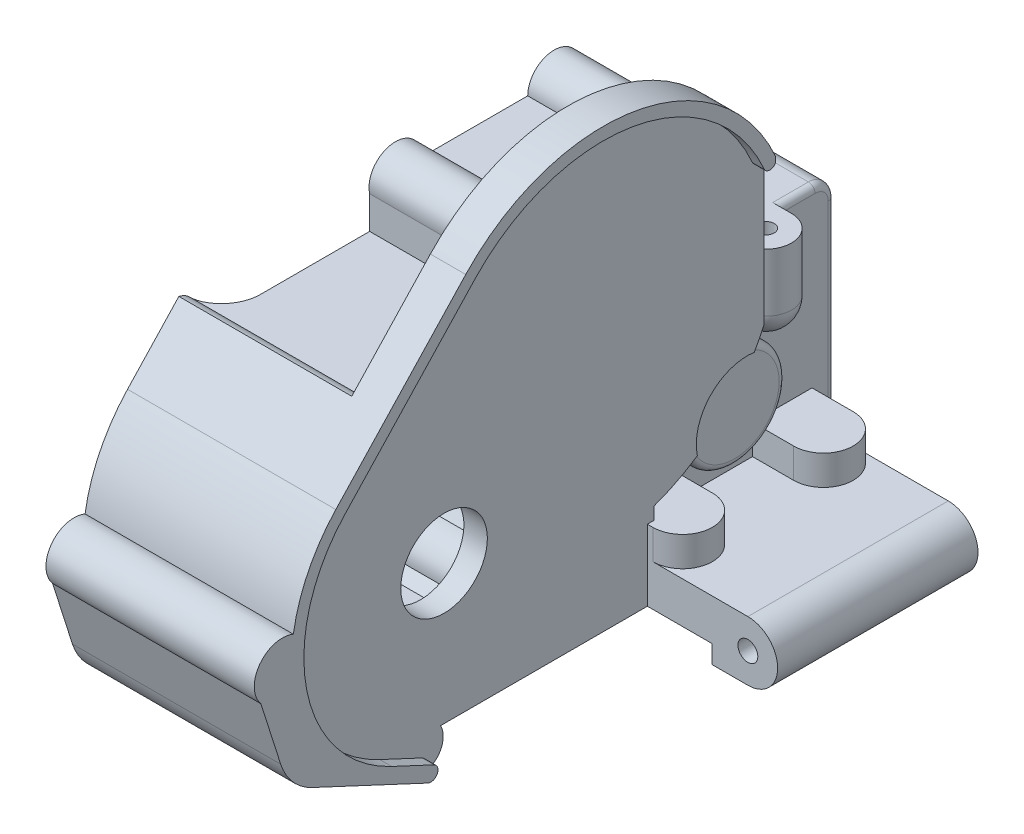
SolidWorks part; units mm, degrees
ref_plane "Front Plane" through (0, 0, 0) normal (0, 0, 1) x (1, 0, 0)
ref_plane "Top Plane" through (0, 0, 0) normal (0, 1, 0) x (1, 0, 0)
ref_plane "Right Plane" through (0, 0, 0) normal (1, 0, 0) x (0, 0, -1)
sketch "Sketch1" plane through (0, 0, 0) normal (0, 0, 1) x (1, 0, 0)
  line L0 (32.75, 0) -> (-32.75, 0) construction
  line L1 (32.75, -4.5) -> (-32.75, -4.5)
  line L2 (32.75, 4.5) -> (-32.75, 4.5)
  line L4 (-27.3, -4.5) -> (27.3, -4.5)
  line L5 (-27.3, -4.5) -> (-27.3, -1.75)
  line L6 (-27.3, -1.75) -> (27.3, -1.75)
  line L7 (27.3, -4.5) -> (27.3, -1.75)
  arc A0 (32.75, -4.5) -> (32.75, 4.5) centre (32.75, 0) ccw
  arc A1 (-32.75, 4.5) -> (-32.75, -4.5) centre (-32.75, 0) ccw
  circle A2 centre (32.75, 0) radius 1.5
  circle A3 centre (-32.75, 0) radius 1.5
  point P2 (0, 0)
  point P12 (0, -1.75)
  dimension "D5" = 3
  dimension "D1" = 65.5
  dimension "D2" = 9
  dimension "D3" = 54.6
  dimension "D4" = 2.75
extrude "Boss-Extrude1" add sketch "Sketch1" along normal blind 30.3 contours L2 A1 L1 L5 L6 L7 A0 region at (0, 0.9599, 0)
sketch "Sketch2" plane through (0, 0, 0) normal (1, 0, 0) x (0, 0, -1)
  line L0 (-35.05, -1.75) -> (3.45, -1.75)
  line L1 (3.45, -1.75) -> (3.45, 32.25)
  line L2 (0.45, 35.25) -> (-15.05, 35.25)
  line L3 (-35.05, 15.25) -> (-35.05, -1.75)
  line L4 (-35.05, -1.75) -> (-70.7928, -1.75)
  line L5 (-30.3, -1.75) -> (0, -1.75) construction
  line L6 (0, -4.5) -> (0, 4.5) construction
  line L7 (-47.969, 0.15) -> (-74.131, 0.15)
  line L8 (-66.9229, -5.75) -> (-82.7794, 1.65)
  line L9 (-87.55, 7.078) -> (-90.55, 16.5114)
  line L11 (-59.5712, 57.2396) -> (-79.2177, 36.2777)
  line L12 (-12.7, 49.25) -> (-12.7, 35.25)
  line L13 (-61.175, -3.35) -> (-61.175, -1.75)
  arc A0 (-15.05, 35.25) -> (-35.05, 15.25) centre (-15.05, 15.25) ccw
  arc A1 (3.45, 32.25) -> (0.45, 35.25) centre (0.45, 32.25) ccw
  circle A2 centre (-61.05, 19.25) radius 23.15
  circle A3 centre (-64.55, -3.35) radius 3.375
  arc A4 (-87.55, 7.078) -> (-82.7794, 1.65) centre (-78.9733, 9.8056) ccw
  circle A5 centre (-87.3, 19.25) radius 4.25
  arc A6 (-85.6407, 23.1627) -> (-79.2177, 36.2777) centre (-61.05, 19.25) cw
  arc A7 (-12.7, 49.25) -> (-59.5712, 57.2396) centre (-38.7768, 37.75) ccw
  point P13 (3.45, 35.25)
  point P30 (-91.55, 19.25)
  point P35 (-38.7768, 66.25)
  dimension "D2" = 20
  dimension "D5" = 3
  dimension "D7" = 46.3
  dimension "D12" = 6.75
  dimension "D13" = 8.5
  dimension "D16" = 9
  dimension "D20" = 1.75
  dimension "D21" = 28.5
  dimension "D1" = 3.45
  dimension "D3" = 37
  dimension "D4" = 18.5
  dimension "D6" = 46
  dimension "D8" = 21
  dimension "D9" = 1.9
  dimension "D10" = 68
  dimension "D11" = 1.6
  dimension "D14" = 95
  dimension "D15" = 1.5
  dimension "D17" = 4
  dimension "D18" = 1
  dimension "D19" = 91
  dimension "D22" = 16.15
  dimension "D23" = 68
  dimension "D24" = 14
extrude "Boss-Extrude2" add sketch "Sketch2" along normal mid plane 24.3 contours L1 A1 L2 A0 L3 L0 | A7 L11 A6 A5 A2 L4 L3 A0 | A5 A2 L7 | A3 L4 A2 L7 | L4 A3 A2 | L4 A3 | A5 L9 A4 L8 A3 A2 | A2 A5 | A3 L4 A2 | A2 A3 | A2 A5 region at (0, 15.8231, 14.8775) region at (0, 43.4679, 39.2022) region at (0, -0.6991, 60.325) region at (0, -4.871, 64.7855) region at (0, -2.6944, 64.2173) region at (0, 20.1783, 60.9898) region at (0, -1.0211, 64.55) region at (0, 5.9046, 81.7148) region at (0, -2.1301, 68.7916) region at (0, 19.25, 87.5929) region at (0, 19.25, 83.7028)
sketch "Sketch3" plane through (0, 35.25, 0) normal (0, 1, 0) x (1, 0, 0)
  line L0 (14, -8.825) -> (-14, -8.825) construction
  line L1 (14, -12.7) -> (-14, -12.7)
  line L2 (14, -4.95) -> (-14, -4.95)
  line L3 (12.15, 3.45) -> (-12.15, 3.45) construction
  arc A0 (14, -12.7) -> (14, -4.95) centre (14, -8.825) ccw
  arc A1 (-14, -4.95) -> (-14, -12.7) centre (-14, -8.825) ccw
  point P2 (0, -8.825)
  point P7 (-17.875, -8.825)
  point P8 (17.875, -8.825)
  dimension "D1" = 28
  dimension "D2" = 7.75
  dimension "D3" = 8.4
extrude "Boss-Extrude3" add sketch "Sketch3" against normal blind 12.66
fillet "Fillet1" radius 3.875 6 edges at (-13.075, 22.59, 4.95) (-13.075, 22.59, 12.7) (13.075, 22.59, 12.7) (13.075, 22.59, 4.95) (-17.875, 22.59, 8.825) (17.875, 22.59, 8.825)
sketch "Sketch4" plane through (0, 4.5, 0) normal (0, 1, 0) x (1, 0, 0)
  line L0 (-18.375, -4.5) -> (18.375, -4.5) construction
  line L1 (-18.375, 0) -> (18.375, 0)
  line L2 (-18.375, -9) -> (18.375, -9)
  line L3 (32.75, 0) -> (12.15, 0) construction
  line L4 (22.875, -4.5) -> (-22.875, -4.5) construction
  line L5 (18.375, -25.8) -> (-18.375, -25.8) construction
  line L6 (18.375, -30.3) -> (-18.375, -30.3)
  line L7 (18.375, -21.3) -> (-18.375, -21.3)
  line L8 (-12.15, -30.3) -> (-32.75, -30.3) construction
  arc A0 (-18.375, 0) -> (-18.375, -9) centre (-18.375, -4.5) ccw
  arc A1 (18.375, -9) -> (18.375, 0) centre (18.375, -4.5) ccw
  arc A2 (18.375, -30.3) -> (18.375, -21.3) centre (18.375, -25.8) ccw
  arc A3 (-18.375, -21.3) -> (-18.375, -30.3) centre (-18.375, -25.8) ccw
  point P2 (0, -4.5)
  point P10 (-22.875, -4.5)
  point P11 (0, -25.8)
  point P13 (22.875, -4.5)
  point P24 (0, 0)
  dimension "D2" = 4.5
  dimension "D1" = 45.75
extrude "Boss-Extrude4" add sketch "Sketch4" along normal blind 4.5
sketch "Sketch5" plane through (0, 35.25, 0) normal (0, 1, 0) x (1, 0, 0)
  circle A0 centre (14, -8.825) radius 1.25
  circle A1 centre (-14, -8.825) radius 1.25
  dimension "D1" = 2.5
extrude "Cut-Extrude1" cut sketch "Sketch5" against normal blind 10
sketch "Sketch6" plane through (0, 0, 0) normal (1, 0, 0) x (0, 0, -1)
  line L0 (-61.5784, -1.75) -> (-30.3, -1.75) construction
  line L3 (-9, 4.5) -> (-21.3, 4.5) construction
  circle A0 centre (-15.15, 15.75) radius 7.75
  point P2 (-7.4, 15.75)
  point P4 (-15.15, 4.5)
  point P5 (0, 0)
  point P8 (0, 0)
  dimension "D1" = 15.5
  dimension "D2" = 17.5
extrude "Boss-Extrude5" add sketch "Sketch6" along normal mid plane 31.16
fillet "Fillet2" radius 1 2 edges at (-15.58, 15.75, 7.4) (15.58, 15.75, 7.4)
fillet "Fillet3" radius 1 6 edges at (12.15, 35.25, 2.25) (12.15, 34.3713, -2.5713) (-12.15, 35.25, 2.25) (-12.15, 34.3713, -2.5713) (12.15, 15.25, -3.45) (-12.15, 15.25, -3.45)
sketch "Sketch7" plane through (0, -1.75, 0) normal (0, -1, 0) x (1, 0, 0)
  line L0 (-27.3, 0) -> (-12.15, 0) construction
  line L1 (0, -4.95) -> (0, 4.95) construction
  circle A0 centre (-19, 5.2) radius 2
  circle A1 centre (-19, 25.2) radius 2
  circle A2 centre (19, 5.2) radius 2
  circle A3 centre (19, 25.2) radius 2
  dimension "D4" = 4
  dimension "D1" = 20
  dimension "D2" = 19
  dimension "D3" = 5.2
extrude "Cut-Extrude2" cut sketch "Sketch7" against normal blind 8
sketch "Sketch9" plane through (12.15, 0, 0) normal (1, 0, 0) x (0, 0, -1)
  line L0 (-29.3, 10.8718) -> (-29.3, 9)
  line L1 (-21.3, 9) -> (-30.3, 9) construction
  line L2 (-29.3, 9) -> (-30.3, 9)
  line L3 (-30.3, 9) -> (-30.3, -1.75)
  line L21 (-12.7, 35.25) -> (-12.7, 49.25)
  line L22 (0.45, 34.25) -> (-4.95, 34.25)
  line L23 (-4.95, 34.25) -> (-4.95, 26.465)
  line L24 (-12.7, 26.465) -> (-12.7, 35.25)
  line L25 (-12.7, 35.25) -> (-12.7, 49.25)
  line L27 (-59.5712, 57.2396) -> (-79.2177, 36.2777)
  line L28 (-90.55, 16.5114) -> (-87.55, 7.078)
  line L29 (-82.7794, 1.65) -> (-66.9229, -5.75)
  line L30 (-61.5784, -1.75) -> (-30.3, -1.75)
  line L31 (-30.3, -1.75) -> (-30.3, 9)
  line L32 (-30.3, 9) -> (-21.3, 9)
  line L33 (-21.3, 9) -> (-21.3, 4.5)
  line L34 (-21.3, 4.5) -> (-9, 4.5)
  line L35 (-9, 4.5) -> (-9, 9)
  line L36 (-9, 9) -> (0, 9)
  line L37 (0, 9) -> (0, -1.75)
  line L38 (0, -1.75) -> (2.45, -1.75)
  line L39 (2.45, -1.75) -> (2.45, 32.25)
  line L40 (0.45, 34.25) -> (-4.95, 34.25)
  line L41 (-4.95, 34.25) -> (-4.95, 26.465)
  line L42 (-12.7, 26.465) -> (-12.7, 35.25)
  line L45 (-59.5712, 57.2396) -> (-79.2177, 36.2777)
  line L46 (-90.55, 16.5114) -> (-87.55, 7.078)
  line L47 (-82.7794, 1.65) -> (-66.9229, -5.75)
  line L48 (-61.5784, -1.75) -> (-30.3, -1.75)
  line L49 (-30.3, -1.75) -> (-30.3, 9)
  line L50 (-30.3, 9) -> (-21.3, 9)
  line L51 (-21.3, 9) -> (-21.3, 4.5)
  line L52 (-21.3, 4.5) -> (-9, 4.5)
  line L53 (-9, 4.5) -> (-9, 9)
  line L54 (-9, 9) -> (0, 9)
  line L55 (0, 9) -> (0, -1.75)
  line L56 (0, -1.75) -> (2.45, -1.75)
  line L57 (2.45, -1.75) -> (2.45, 32.25)
  circle A0 centre (-38.7768, 37.75) radius 28.5
  circle A1 centre (-15.15, 15.75) radius 7.75 construction
  circle A2 centre (-15.15, 15.75) radius 7.75
  arc A12 (2.45, 32.25) -> (0.45, 34.25) centre (0.45, 32.25) ccw
  arc A13 (-8.825, 22.59) -> (-4.95, 26.465) centre (-8.825, 26.465) ccw
  arc A14 (-12.7, 26.465) -> (-8.825, 22.59) centre (-8.825, 26.465) ccw
  arc A15 (-12.7, 49.25) -> (-59.5712, 57.2396) centre (-38.7768, 37.75) ccw
  arc A16 (-79.2177, 36.2777) -> (-85.6407, 23.1627) centre (-61.05, 19.25) ccw
  arc A17 (-85.6407, 23.1627) -> (-90.55, 16.5114) centre (-87.3, 19.25) ccw
  arc A18 (-87.55, 7.078) -> (-82.7794, 1.65) centre (-78.9733, 9.8056) ccw
  arc A19 (-66.9229, -5.75) -> (-61.5784, -1.75) centre (-64.55, -3.35) ccw
  arc A21 (2.45, 32.25) -> (0.45, 34.25) centre (0.45, 32.25) ccw
  arc A22 (-8.825, 22.59) -> (-4.95, 26.465) centre (-8.825, 26.465) ccw
  arc A23 (-12.7, 26.465) -> (-8.825, 22.59) centre (-8.825, 26.465) ccw
  arc A24 (-12.7, 49.25) -> (-59.5712, 57.2396) centre (-38.7768, 37.75) ccw
  arc A25 (-79.2177, 36.2777) -> (-85.6407, 23.1627) centre (-61.05, 19.25) ccw
  arc A26 (-85.6407, 23.1627) -> (-90.55, 16.5114) centre (-87.3, 19.25) ccw
  arc A27 (-87.55, 7.078) -> (-82.7794, 1.65) centre (-78.9733, 9.8056) ccw
  arc A28 (-66.9229, -5.75) -> (-61.5784, -1.75) centre (-64.55, -3.35) ccw
  point P11 (-29.3, 9.9359)
  circle M31 centre (-15.15, 15.75) radius 7.75
  arc M36 (-8.825, 22.59) -> (-12.7, 26.465) centre (-8.825, 26.465) cw
  line M37 (-12.7, 26.465) -> (-12.7, 35.25)
  arc M40 (-12.7, 49.25) -> (-59.5712, 57.2396) centre (-38.7768, 37.75) ccw
  line M41 (-59.5712, 57.2396) -> (-79.2177, 36.2777)
  arc M42 (-79.2177, 36.2777) -> (-85.6407, 23.1627) centre (-61.05, 19.25) ccw
  arc M43 (-85.6407, 23.1627) -> (-90.55, 16.5114) centre (-87.3, 19.25) ccw
  line M44 (-90.55, 16.5114) -> (-87.55, 7.078)
  arc M45 (-87.55, 7.078) -> (-82.7794, 1.65) centre (-78.9733, 9.8056) ccw
  line M46 (-82.7794, 1.65) -> (-66.9229, -5.75)
  arc M47 (-66.9229, -5.75) -> (-61.5784, -1.75) centre (-64.55, -3.35) ccw
  line M49 (-61.5784, -1.75) -> (-30.3, -1.75)
  line M50 (-30.3, -1.75) -> (-30.3, 9)
  line M51 (-30.3, 9) -> (-21.3, 9)
  line M91 (-12.7, 35.25) -> (-12.7, 49.25)
  dimension "D2" = 1
  dimension "D1" = 0
extrude "Boss-Extrude6" add sketch "Sketch9" along normal offset from surface (5.4 mm away) 29.7 contours A0 L0 M41 M42 M43 M44 M45 M46 M47 M49 M50 M51 | A0 M40 M31 M36 M37 M91 region at (12.15, 14.0433, 66.1845) region at (12.15, 38.0059, 39.4606) up to face at (-12.15, 15.75, 7.4)
sketch "Sketch10" plane through (17.55, 0, 0) normal (1, 0, 0) x (0, 0, -1)
  line L0 (-58.1849, 55.9403) -> (-77.8314, 34.9784)
  line L2 (-66.9229, -5.75) -> (-65.2918, -6.5112)
  line L3 (-70.7767, -1.5921) -> (-64.3876, -4.5738)
  line L8 (-29.3, 9) -> (-29.3, 10.8718)
  line L9 (-12.7, 26.465) -> (-12.7, 49.25)
  line L10 (-59.5712, 57.2396) -> (-79.2177, 36.2777)
  line L11 (-90.55, 16.5114) -> (-87.55, 7.078)
  line L12 (-82.7794, 1.65) -> (-66.9229, -5.75)
  line L13 (-61.5784, -1.75) -> (-30.3, -1.75)
  line L14 (-30.3, -1.75) -> (-30.3, 9)
  line L15 (-30.3, 9) -> (-29.3, 9)
  line L16 (-29.3, 9) -> (-29.3, 10.8718)
  line L17 (-12.7, 26.465) -> (-12.7, 49.25)
  line L18 (-59.5712, 57.2396) -> (-79.2177, 36.2777)
  line L19 (-90.55, 16.5114) -> (-87.55, 7.078)
  line L20 (-82.7794, 1.65) -> (-66.9229, -5.75)
  line L21 (-61.5784, -1.75) -> (-30.3, -1.75)
  line L22 (-30.3, -1.75) -> (-30.3, 9)
  line L23 (-30.3, 9) -> (-29.3, 9)
  circle A0 centre (-61.05, 19.25) radius 23
  arc A1 (-14.4385, 48.4833) -> (-58.1849, 55.9403) centre (-38.7768, 37.75) ccw
  arc A2 (-12.7, 49.25) -> (-14.4385, 48.4833) centre (-13.5692, 48.8667) cw
  arc A5 (-65.2918, -6.5112) -> (-64.3876, -4.5738) centre (-64.8397, -5.5425) ccw
  arc A10 (-29.3, 10.8718) -> (-22.7412, 14.1892) centre (-38.7768, 37.75) ccw
  arc A11 (-14.1338, 23.4331) -> (-22.7412, 14.1892) centre (-15.15, 15.75) ccw
  arc A12 (-14.1338, 23.4331) -> (-12.6947, 26.2621) centre (-38.7768, 37.75) ccw
  arc A13 (-12.7, 26.465) -> (-12.6947, 26.2621) centre (-8.825, 26.465) ccw
  arc A14 (-12.7, 49.25) -> (-59.5712, 57.2396) centre (-38.7768, 37.75) ccw
  arc A15 (-79.2177, 36.2777) -> (-85.6407, 23.1627) centre (-61.05, 19.25) ccw
  arc A16 (-85.6407, 23.1627) -> (-90.55, 16.5114) centre (-87.3, 19.25) ccw
  arc A17 (-87.55, 7.078) -> (-82.7794, 1.65) centre (-78.9733, 9.8056) ccw
  arc A18 (-66.9229, -5.75) -> (-61.5784, -1.75) centre (-64.55, -3.35) ccw
  arc A20 (-29.3, 10.8718) -> (-22.7412, 14.1892) centre (-38.7768, 37.75) ccw
  arc A21 (-14.1338, 23.4331) -> (-22.7412, 14.1892) centre (-15.15, 15.75) ccw
  arc A22 (-14.1338, 23.4331) -> (-12.6947, 26.2621) centre (-38.7768, 37.75) ccw
  arc A23 (-12.7, 26.465) -> (-12.6947, 26.2621) centre (-8.825, 26.465) ccw
  arc A24 (-12.7, 49.25) -> (-59.5712, 57.2396) centre (-38.7768, 37.75) ccw
  arc A25 (-79.2177, 36.2777) -> (-85.6407, 23.1627) centre (-61.05, 19.25) ccw
  arc A26 (-85.6407, 23.1627) -> (-90.55, 16.5114) centre (-87.3, 19.25) ccw
  arc A27 (-87.55, 7.078) -> (-82.7794, 1.65) centre (-78.9733, 9.8056) ccw
  arc A28 (-66.9229, -5.75) -> (-61.5784, -1.75) centre (-64.55, -3.35) ccw
  point P32 (-64.55, -5.509)
  point P34 (-64.8384, -5.5431)
  arc M31 (-12.7, 49.25) -> (-59.5712, 57.2396) centre (-38.7768, 37.75) ccw
  line M32 (-59.5712, 57.2396) -> (-79.2177, 36.2777)
  arc M33 (-79.2177, 36.2777) -> (-85.6407, 23.1627) centre (-61.05, 19.25) ccw
  arc M34 (-85.6407, 23.1627) -> (-90.55, 16.5114) centre (-87.3, 19.25) ccw
  line M35 (-90.55, 16.5114) -> (-87.55, 7.078)
  arc M36 (-87.55, 7.078) -> (-82.7794, 1.65) centre (-78.9733, 9.8056) ccw
  line M37 (-82.7794, 1.65) -> (-66.9229, -5.75)
  dimension "D2" = 1.9
  dimension "D3" = 1.9
  dimension "D4" = 1.8
  dimension "D1" = 0
extrude "Boss-Extrude7" add sketch "Sketch10" along normal offset from surface (1.8 mm away) 31.5 contours L2 A5 L3 A0 L0 A1 A2 L17 M31 M32 M33 M34 M35 M36 M37 region at (17.55, 46.1935, 68.7915) up to face at (-12.15, 15.75, 7.4)
sketch "Sketch8" plane through (-12.15, 0, 0) normal (-1, 0, 0) x (0, 0, 1)
  line L0 (35.05, -1.75) -> (-3.45, -1.75) construction
  line L1 (-3.45, -1.75) -> (-3.45, 32.25) construction
  line L2 (-0.45, 35.25) -> (15.05, 35.25) construction
  line L4 (59.5712, 57.2396) -> (79.2177, 36.2777) construction
  line L5 (35.05, 15.25) -> (35.05, -1.75) construction
  line L6 (35.05, -1.75) -> (70.7928, -1.75) construction
  line L7 (66.9229, -5.75) -> (82.7794, 1.65) construction
  line L8 (87.55, 7.078) -> (90.55, 16.5114) construction
  line L9 (47.969, 0.15) -> (74.131, 0.15) construction
  line L10 (35.05, -1.75) -> (-3.45, -1.75)
  line L11 (-3.45, -1.75) -> (-3.45, 32.25)
  line L12 (-0.45, 35.25) -> (15.05, 35.25)
  line L14 (59.5712, 57.2396) -> (79.2177, 36.2777)
  line L15 (35.05, 15.25) -> (35.05, -1.75)
  line L16 (35.05, -1.75) -> (70.7928, -1.75)
  line L17 (66.9229, -5.75) -> (82.7794, 1.65)
  line L18 (87.55, 7.078) -> (90.55, 16.5114)
  line L19 (47.969, 0.15) -> (74.131, 0.15)
  line L20 (77.9409, 35.081) -> (72.2527, 41.15)
  line L21 (72.2527, 41.15) -> (50.6527, 41.15)
  line L22 (50.6527, 38.6228) -> (50.6527, 41.15)
  line L23 (42.1867, 29.7028) -> (40.1236, 29.15)
  line L24 (70.0027, 41.15) -> (70.0027, 38.469)
  arc A0 (-0.45, 35.25) -> (-3.45, 32.25) centre (-0.45, 32.25) ccw construction
  circle A1 centre (61.05, 19.25) radius 23.15
  circle A2 centre (61.05, 19.25) radius 23.15
  circle A3 centre (87.3, 19.25) radius 4.25
  circle A4 centre (87.3, 19.25) radius 4.25
  circle A5 centre (64.55, -3.35) radius 3.375
  circle A6 centre (64.55, -3.35) radius 3.375
  arc A7 (59.5712, 57.2396) -> (12.7, 49.25) centre (38.7768, 37.75) ccw construction
  arc A8 (85.6407, 23.1627) -> (79.2177, 36.2777) centre (61.05, 19.25) ccw construction
  arc A9 (35.05, 15.25) -> (15.05, 35.25) centre (15.05, 15.25) ccw construction
  arc A10 (82.7794, 1.65) -> (87.55, 7.078) centre (78.9733, 9.8056) ccw construction
  arc A11 (-0.45, 35.25) -> (-3.45, 32.25) centre (-0.45, 32.25) ccw
  arc A12 (59.5712, 57.2396) -> (12.7, 49.25) centre (38.7768, 37.75) ccw
  arc A13 (85.6407, 23.1627) -> (79.2177, 36.2777) centre (61.05, 19.25) ccw
  arc A14 (35.05, 15.25) -> (15.05, 35.25) centre (15.05, 15.25) ccw
  arc A15 (82.7794, 1.65) -> (87.55, 7.078) centre (78.9733, 9.8056) ccw
  arc A16 (43.3544, 30.5577) -> (49.7307, 36.9382) centre (61.05, 19.25) cw
  arc A17 (43.3544, 30.5577) -> (42.1867, 29.7028) centre (41.6691, 31.6346) cw
  arc A18 (49.7307, 36.9382) -> (50.6527, 38.6228) centre (48.6527, 38.6228) ccw
  circle A19 centre (42.05, 1.8) radius 4.25
  circle A20 centre (72.2527, 41.15) radius 3.5
  point P48 (51.2409, 41.15)
  point P49 (70.049, 38.469)
  dimension "D5" = 2
  dimension "D8" = 8.5
  dimension "D10" = 21
  dimension "D12" = 7
  dimension "D4" = 41
  dimension "D6" = 3.55
  dimension "D7" = 45.5
  dimension "D9" = 12
  dimension "D11" = 105
  dimension "D13" = 19.35
  dimension "D14" = 2.25
  dimension "D1" = 0
  dimension "D2" = 0
  dimension "D3" = 0
extrude "Cut-Extrude3" cut sketch "Sketch8" against normal blind 26.15 and the other way through all contours A20 A2 L21 L22 A18 A16 A17 L23 A19 L19 A4 | A2 A20 L24 | L21 A20 A2 L24 | A20 L21 A2 region at (-12.15, 19.7067, 61.283) region at (-12.15, 41.127, 68.6868) region at (-12.15, 40.9664, 69.5434) region at (-12.15, 39.95, 69.4846)
sketch "Sketch11" plane through (-12.15, 0, 0) normal (-1, 0, 0) x (0, 0, 1)
  line L0 (12.7, 35.25) -> (4.95, 35.25) construction
  line L1 (12.7, 35.0955) -> (12.7, 36.75)
  line L2 (12.7, 49.25) -> (12.7, 35.25) construction
  line L3 (12.7, 35.25) -> (12.7941, 35.25)
  line L4 (70.0027, 41.15) -> (53.5458, 41.15) construction
  line L5 (69.8032, 43.65) -> (47.6032, 43.65)
  line L6 (35.1146, 24.75) -> (38.5628, 24.75)
  line L7 (61.5784, -1.75) -> (30.3, -1.75) construction
  line L8 (47.6032, 43.65) -> (47.6032, 48.5754)
  line L9 (23.7, 49.45) -> (39.7, 49.45)
  line L26 (4.95, 26.465) -> (4.95, 34.25)
  line L27 (4.95, 34.25) -> (-0.45, 34.25)
  line L28 (-2.45, 32.25) -> (-2.45, -1.75)
  line L29 (-2.45, -1.75) -> (0, -1.75)
  line L30 (0, -1.75) -> (0, 9)
  line L31 (0, 9) -> (9, 9)
  line L32 (9, 9) -> (9, 4.5)
  line L33 (9, 4.5) -> (21.3, 4.5)
  line L34 (21.3, 4.5) -> (21.3, 9)
  line L35 (21.3, 9) -> (30.3, 9)
  line L36 (30.3, 9) -> (30.3, -1.75)
  line L37 (30.3, -1.75) -> (61.5784, -1.75)
  line L38 (66.9229, -5.75) -> (82.7794, 1.65)
  line L39 (87.55, 7.078) -> (90.55, 16.5114)
  line L40 (79.2177, 36.2777) -> (59.5712, 57.2396)
  line L41 (12.7, 49.25) -> (12.7, 35.25)
  line L42 (12.7, 35.25) -> (12.7, 26.465)
  line L43 (4.95, 26.465) -> (4.95, 34.25)
  line L44 (4.95, 34.25) -> (-0.45, 34.25)
  line L45 (-2.45, 32.25) -> (-2.45, -1.75)
  line L46 (-2.45, -1.75) -> (0, -1.75)
  line L47 (0, -1.75) -> (0, 9)
  line L48 (0, 9) -> (9, 9)
  line L49 (9, 9) -> (9, 4.5)
  line L50 (9, 4.5) -> (21.3, 4.5)
  line L51 (21.3, 4.5) -> (21.3, 9)
  line L52 (21.3, 9) -> (30.3, 9)
  line L53 (30.3, 9) -> (30.3, -1.75)
  line L54 (30.3, -1.75) -> (61.5784, -1.75)
  line L55 (66.9229, -5.75) -> (82.7794, 1.65)
  line L56 (87.55, 7.078) -> (90.55, 16.5114)
  line L57 (79.2177, 36.2777) -> (59.5712, 57.2396)
  line L58 (12.7, 49.25) -> (12.7, 35.25)
  line L59 (12.7, 35.25) -> (12.7, 26.465)
  arc A0 (31.2767, 26.7127) -> (12.8127, 35.1094) centre (24.7, 36.75) ccw
  arc A1 (31.2767, 26.7127) -> (12.7, 35.0955) centre (15.15, 15.75) ccw
  circle A2 centre (19.7, 49.45) radius 4
  circle A3 centre (43.7, 49.45) radius 4
  circle A4 centre (72.2527, 41.15) radius 3.5
  circle A5 centre (35.1146, 29.4802) radius 4.7302
  arc A6 (40.1236, 29.15) -> (42.0321, 6.05) centre (61.05, 19.25) ccw construction
  arc A16 (-0.45, 34.25) -> (-2.45, 32.25) centre (-0.45, 32.25) ccw
  arc A18 (61.5784, -1.75) -> (66.9229, -5.75) centre (64.55, -3.35) ccw
  arc A19 (82.7794, 1.65) -> (87.55, 7.078) centre (78.9733, 9.8056) ccw
  arc A20 (90.55, 16.5114) -> (85.6407, 23.1627) centre (87.3, 19.25) ccw
  arc A21 (85.6407, 23.1627) -> (79.2177, 36.2777) centre (61.05, 19.25) ccw
  arc A22 (59.5712, 57.2396) -> (12.7, 49.25) centre (38.7768, 37.75) ccw
  arc A23 (8.825, 22.59) -> (12.7, 26.465) centre (8.825, 26.465) ccw
  arc A24 (4.95, 26.465) -> (8.825, 22.59) centre (8.825, 26.465) ccw
  arc A25 (-0.45, 34.25) -> (-2.45, 32.25) centre (-0.45, 32.25) ccw
  arc A27 (61.5784, -1.75) -> (66.9229, -5.75) centre (64.55, -3.35) ccw
  arc A28 (82.7794, 1.65) -> (87.55, 7.078) centre (78.9733, 9.8056) ccw
  arc A29 (90.55, 16.5114) -> (85.6407, 23.1627) centre (87.3, 19.25) ccw
  arc A30 (85.6407, 23.1627) -> (79.2177, 36.2777) centre (61.05, 19.25) ccw
  arc A31 (59.5712, 57.2396) -> (12.7, 49.25) centre (38.7768, 37.75) ccw
  arc A32 (8.825, 22.59) -> (12.7, 26.465) centre (8.825, 26.465) ccw
  arc A33 (4.95, 26.465) -> (8.825, 22.59) centre (8.825, 26.465) ccw
  line M25 (79.2177, 36.2777) -> (59.5712, 57.2396)
  arc M26 (59.5712, 57.2396) -> (12.7, 49.25) centre (38.7768, 37.75) ccw
  line M27 (12.7, 49.25) -> (12.7, 35.25)
  dimension "D4" = 8
  dimension "D9" = 22.2
  dimension "D1" = 1.5
  dimension "D2" = 12
  dimension "D3" = 24
  dimension "D5" = 8.3
  dimension "D6" = 7
  dimension "D7" = 2.5
  dimension "D8" = 26.5
  dimension "D10" = 0
extrude "Cut-Extrude4" cut sketch "Sketch11" against normal up to surface (26.15 mm away) contours A4 A0 A2 L9 A3 L8 L5 M25 M26 M27 region at (-12.15, 54.6329, 42.036) up to face at (14, 25.6446, 57.7079)
sketch "Sketch12" plane through (-12.15, 0, 0) normal (-1, 0, 0) x (0, 0, 1)
  line L0 (12.7, 35.0955) -> (12.7, 36.75) construction
  line L1 (12.7, 35.25) -> (12.7941, 35.25) construction
  line L2 (35.1146, 24.75) -> (38.5628, 24.75) construction
  line L3 (69.8032, 43.65) -> (47.6032, 43.65) construction
  line L4 (47.6032, 43.65) -> (47.6032, 48.5754) construction
  line L5 (23.7, 49.45) -> (39.7, 49.45) construction
  line L6 (12.7, 35.0955) -> (12.7, 36.75)
  line L7 (12.7, 35.25) -> (12.7941, 35.25)
  line L8 (35.1146, 24.75) -> (38.5628, 24.75)
  line L9 (69.8032, 43.65) -> (47.6032, 43.65)
  line L10 (47.6032, 43.65) -> (47.6032, 48.5754)
  line L11 (23.7, 49.45) -> (39.7, 49.45)
  line L17 (79.2177, 36.2777) -> (59.5712, 57.2396)
  line L18 (12.7, 49.25) -> (12.7, 35.25)
  line L19 (12.7, 35.25) -> (12.7, 26.465)
  line L20 (4.95, 26.465) -> (4.95, 34.25)
  line L21 (4.95, 34.25) -> (-0.45, 34.25)
  line L22 (-2.45, 32.25) -> (-2.45, -1.75)
  line L23 (-2.45, -1.75) -> (0, -1.75)
  line L24 (0, -1.75) -> (0, 9)
  line L25 (0, 9) -> (9, 9)
  line L26 (9, 9) -> (9, 4.5)
  line L27 (9, 4.5) -> (21.3, 4.5)
  line L28 (21.3, 4.5) -> (21.3, 9)
  line L29 (21.3, 9) -> (30.3, 9)
  line L30 (30.3, 9) -> (30.3, -1.75)
  line L31 (30.3, -1.75) -> (61.5784, -1.75)
  line L32 (66.9229, -5.75) -> (82.7794, 1.65)
  line L33 (87.55, 7.078) -> (90.55, 16.5114)
  line L34 (79.2177, 36.2777) -> (59.5712, 57.2396)
  line L35 (12.7, 49.25) -> (12.7, 35.25)
  line L36 (12.7, 35.25) -> (12.7, 26.465)
  line L37 (4.95, 26.465) -> (4.95, 34.25)
  line L38 (4.95, 34.25) -> (-0.45, 34.25)
  line L39 (-2.45, 32.25) -> (-2.45, -1.75)
  line L40 (-2.45, -1.75) -> (0, -1.75)
  line L41 (0, -1.75) -> (0, 9)
  line L42 (0, 9) -> (9, 9)
  line L43 (9, 9) -> (9, 4.5)
  line L44 (9, 4.5) -> (21.3, 4.5)
  line L45 (21.3, 4.5) -> (21.3, 9)
  line L46 (21.3, 9) -> (30.3, 9)
  line L47 (30.3, 9) -> (30.3, -1.75)
  line L48 (30.3, -1.75) -> (61.5784, -1.75)
  line L49 (66.9229, -5.75) -> (82.7794, 1.65)
  line L50 (87.55, 7.078) -> (90.55, 16.5114)
  arc A0 (31.2767, 26.7127) -> (12.7, 35.0955) centre (15.15, 15.75) ccw construction
  circle A1 centre (19.7, 49.45) radius 4
  circle A2 centre (19.7, 49.45) radius 4
  circle A3 centre (35.1146, 29.4802) radius 4.7302
  circle A4 centre (35.1146, 29.4802) radius 4.7302
  circle A5 centre (72.2527, 41.15) radius 3.5
  circle A6 centre (72.2527, 41.15) radius 3.5
  circle A7 centre (43.7, 49.45) radius 4
  circle A8 centre (43.7, 49.45) radius 4
  arc A9 (31.2767, 26.7127) -> (12.8127, 35.1094) centre (24.7, 36.75) ccw construction
  arc A10 (31.2767, 26.7127) -> (12.7, 35.0955) centre (15.15, 15.75) ccw
  arc A11 (31.2767, 26.7127) -> (12.8127, 35.1094) centre (24.7, 36.75) ccw
  arc A17 (59.5712, 57.2396) -> (12.7, 49.25) centre (38.7768, 37.75) ccw
  arc A18 (8.825, 22.59) -> (12.7, 26.465) centre (8.825, 26.465) ccw
  arc A19 (4.95, 26.465) -> (8.825, 22.59) centre (8.825, 26.465) ccw
  arc A20 (-0.45, 34.25) -> (-2.45, 32.25) centre (-0.45, 32.25) ccw
  arc A22 (61.5784, -1.75) -> (66.9229, -5.75) centre (64.55, -3.35) ccw
  arc A23 (82.7794, 1.65) -> (87.55, 7.078) centre (78.9733, 9.8056) ccw
  arc A24 (90.55, 16.5114) -> (85.6407, 23.1627) centre (87.3, 19.25) ccw
  arc A25 (85.6407, 23.1627) -> (79.2177, 36.2777) centre (61.05, 19.25) ccw
  arc A26 (59.5712, 57.2396) -> (12.7, 49.25) centre (38.7768, 37.75) ccw
  arc A27 (8.825, 22.59) -> (12.7, 26.465) centre (8.825, 26.465) ccw
  arc A28 (4.95, 26.465) -> (8.825, 22.59) centre (8.825, 26.465) ccw
  arc A29 (-0.45, 34.25) -> (-2.45, 32.25) centre (-0.45, 32.25) ccw
  arc A31 (61.5784, -1.75) -> (66.9229, -5.75) centre (64.55, -3.35) ccw
  arc A32 (82.7794, 1.65) -> (87.55, 7.078) centre (78.9733, 9.8056) ccw
  arc A33 (90.55, 16.5114) -> (85.6407, 23.1627) centre (87.3, 19.25) ccw
  arc A34 (85.6407, 23.1627) -> (79.2177, 36.2777) centre (61.05, 19.25) ccw
  arc M39 (42.0321, 6.05) -> (40.1236, 29.15) centre (61.05, 19.25) cw
  line M40 (40.1236, 29.15) -> (42.1867, 29.7028)
  arc M41 (42.1867, 29.7028) -> (43.3544, 30.5577) centre (41.6691, 31.6346) ccw
  arc M42 (43.3544, 30.5577) -> (49.7307, 36.9382) centre (61.05, 19.25) cw
  arc M43 (49.7307, 36.9382) -> (50.6527, 38.6228) centre (48.6527, 38.6228) ccw
  line M44 (50.6527, 38.6228) -> (50.6527, 39.9338)
  arc M45 (50.6527, 39.9338) -> (53.5458, 41.15) centre (61.05, 19.25) cw
  line M46 (53.5458, 41.15) -> (70.0027, 41.15)
  line M49 (69.8032, 43.65) -> (47.6032, 43.65)
  line M50 (47.6032, 43.65) -> (47.6032, 48.5754)
  arc M51 (47.6032, 48.5754) -> (39.7, 49.45) centre (43.7, 49.45) ccw
  line M52 (39.7, 49.45) -> (23.7, 49.45)
  arc M54 (17.335, 46.224) -> (12.7, 36.75) centre (24.7, 36.75) ccw
  dimension "D1" = 0
  dimension "D2" = 0
  dimension "D3" = 0
  dimension "D4" = 0
  dimension "D5" = 0
extrude "Cut-Extrude5" cut sketch "Sketch12" against normal blind 5 contours A11 A10 A4 A2 M54 | A11 A4 A6 A8 A2 M39 M40 M41 M42 M43 M44 M45 M46 M49 M50 M52 | A8 M51 | A2 region at (-12.15, 39.642, 25.3836) region at (-12.15, 41.0782, 44.1834) region at (-12.15, 49.45, 43.7)
fillet "Fillet4" radius 0.25 1 edges at (-9.65, 26.7998, 31.2171)
fillet "Fillet5" radius 5 1 edges at (-7.15, 42.5059, 69.026)
sketch "Sketch13" plane through (14, 0, 0) normal (-1, 0, 0) x (0, 0, 1)
  circle A0 centre (61.05, 19.25) radius 6.55
  dimension "D1" = 13.1
extrude "Cut-Extrude6" cut sketch "Sketch13" against normal through all
